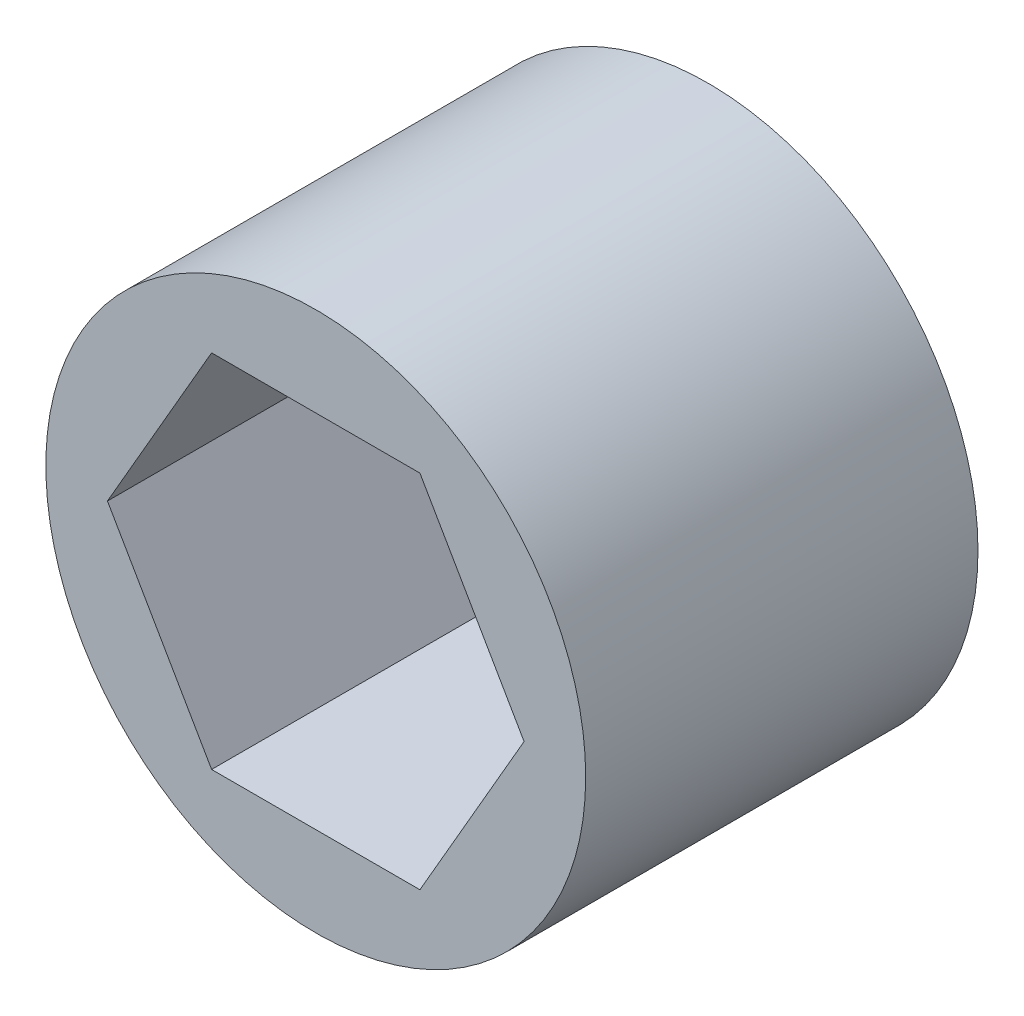
SolidWorks part; units mm, degrees
ref_plane "Front Plane" through (0, 0, 0) normal (0, 0, 1) x (1, 0, 0)
ref_plane "Top Plane" through (0, 0, 0) normal (0, 1, 0) x (1, 0, 0)
ref_plane "Right Plane" through (0, 0, 0) normal (1, 0, 0) x (0, 0, -1)
sketch "Sketch1" plane through (0, 0, 0) normal (0, 0, 1) x (1, 0, 0)
  line L1 (5.7879, 0) -> (2.894, 5.0125)
  line L2 (2.894, 5.0125) -> (-2.894, 5.0125)
  line L3 (-2.894, 5.0125) -> (-5.7879, 0)
  line L4 (-5.7879, 0) -> (-2.894, -5.0125)
  line L5 (-2.894, -5.0125) -> (2.894, -5.0125)
  line L6 (2.894, -5.0125) -> (5.7879, 0)
  circle A0 centre (0, 0) radius 7.5
  circle A1 centre (0, 0) radius 5.0125 construction
  dimension "D1" = 10.025
  dimension "D2" = 15
extrude "Boss-Extrude1" add sketch "Sketch1" along normal mid plane 10.9
ref_axis "Axis1" through (0, 0, -13.3344) along (0, 0, 1)
